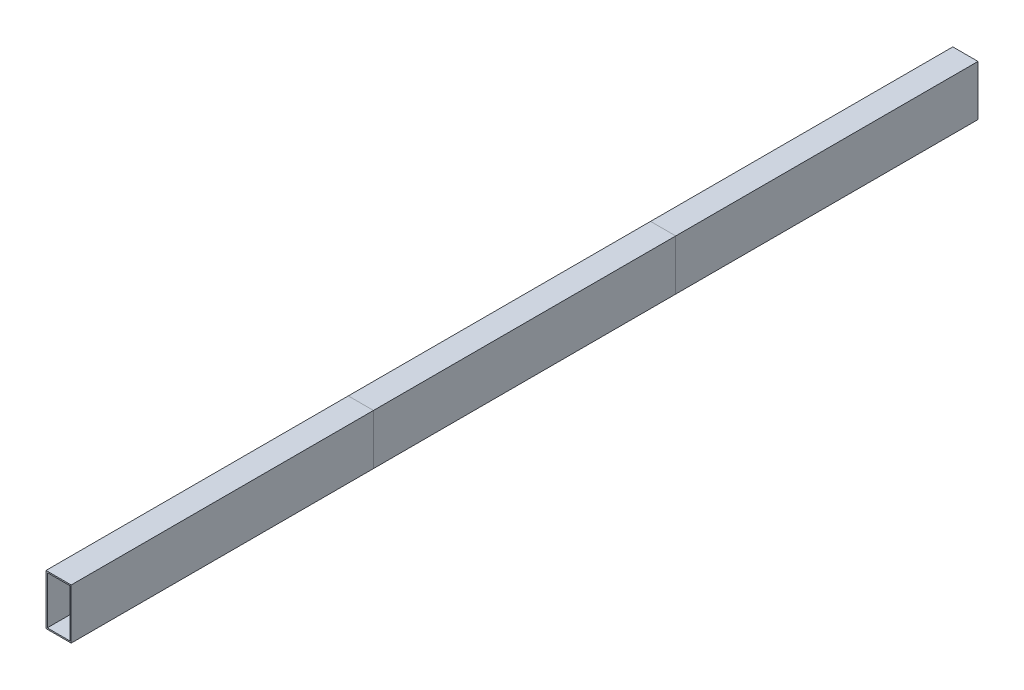
SolidWorks part; units mm, degrees
ref_plane "Спереди" through (0, 0, 0) normal (0, 0, 1) x (1, 0, 0)
ref_plane "Сверху" through (0, 0, 0) normal (0, 1, 0) x (1, 0, 0)
ref_plane "Справа" through (0, 0, 0) normal (1, 0, 0) x (0, 0, -1)
sketch "Эскиз2" plane through (0, 0, 0) normal (0, 0, 1) x (1, 0, 0)
  line L1 (-50, -100) -> (50, -100)
  line L2 (-50, -100) -> (-50, 100)
  line L3 (-50, 100) -> (50, 100)
  line L4 (50, -100) -> (50, 100)
  line L5 (-50, -100) -> (50, 100) construction
  line L6 (-50, 100) -> (50, -100) construction
  line L7 (-45, -95) -> (45, -95)
  line L8 (-45, -95) -> (-45, 95)
  line L9 (-45, 95) -> (45, 95)
  line L10 (45, -95) -> (45, 95)
  line L11 (-45, -95) -> (45, 95) construction
  line L12 (-45, 95) -> (45, -95) construction
  point P0 (0, 0)
  point P6 (0, 0)
  dimension "D1" = 100
  dimension "D2" = 200
  dimension "D3" = 90
  dimension "D4" = 190
extrude "Бобышка-Вытянуть1" add sketch "Эскиз2" along normal blind 1200
extrude "Бобышка-Вытянуть2" add sketch "Эскиз2<2>" along normal blind 1200 from surface separate body starting at face at (0, 0, 1200)
sketch "Эскиз2<2>" plane through (0, 0, 0) normal (0, 0, 1) x (1, 0, 0) same geometry as "Эскиз2"
extrude "Бобышка-Вытянуть3" add sketch "Эскиз2<3>" along normal blind 1200 from surface separate body starting at face at (0, 0, 2400)
sketch "Эскиз2<3>" plane through (0, 0, 0) normal (0, 0, 1) x (1, 0, 0) same geometry as "Эскиз2"
ref_point "Точка1"
ref_point "Точка2"
